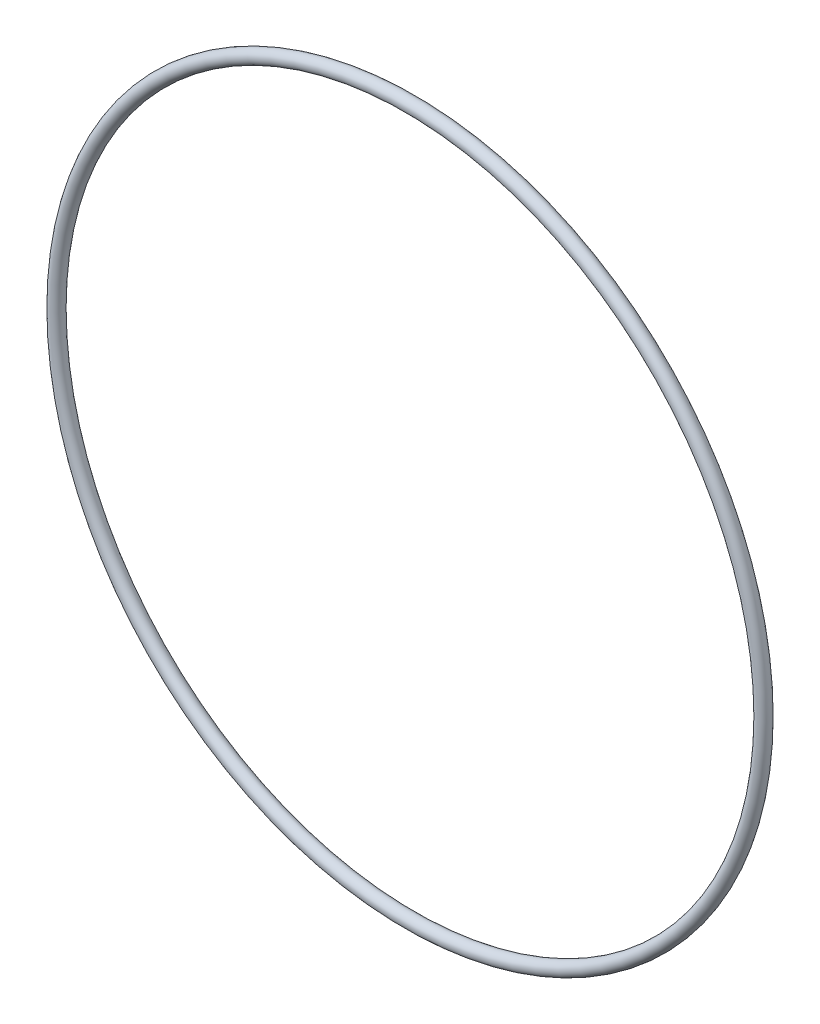
SolidWorks part; units mm, degrees
ref_plane "Front" through (0, 0, 0) normal (0, 0, 1) x (1, 0, 0)
ref_plane "Top" through (0, 0, 0) normal (0, 1, 0) x (1, 0, 0)
ref_plane "Right" through (0, 0, 0) normal (1, 0, 0) x (0, 0, -1)
sketch "Sketch1" plane through (0, 0, 0) normal (1, 0, 0) x (0, -1, 0)
  line L0 (0, -1.3081) -> (0, 1.3081) construction
  line L2 (-76.0387, 0) -> (76.0387, 0) construction
  line L3 (-66.5099, 0) -> (66.5099, 0) construction
  circle A0 centre (67.818, 0) radius 1.3081
  point P9 (66.5099, 0)
  point P10 (69.1261, 0)
  point P13 (67.818, 1.3081)
  point P14 (67.818, -1.3081)
  dimension "Width" = 2.6162
  dimension "ID" = 133.0198
revolve "Revolve1" add sketch "Sketch1" angle 360 about L0
ref_axis "Axis1" through (0, 0, 1.4389) along (0, 0, -1)
